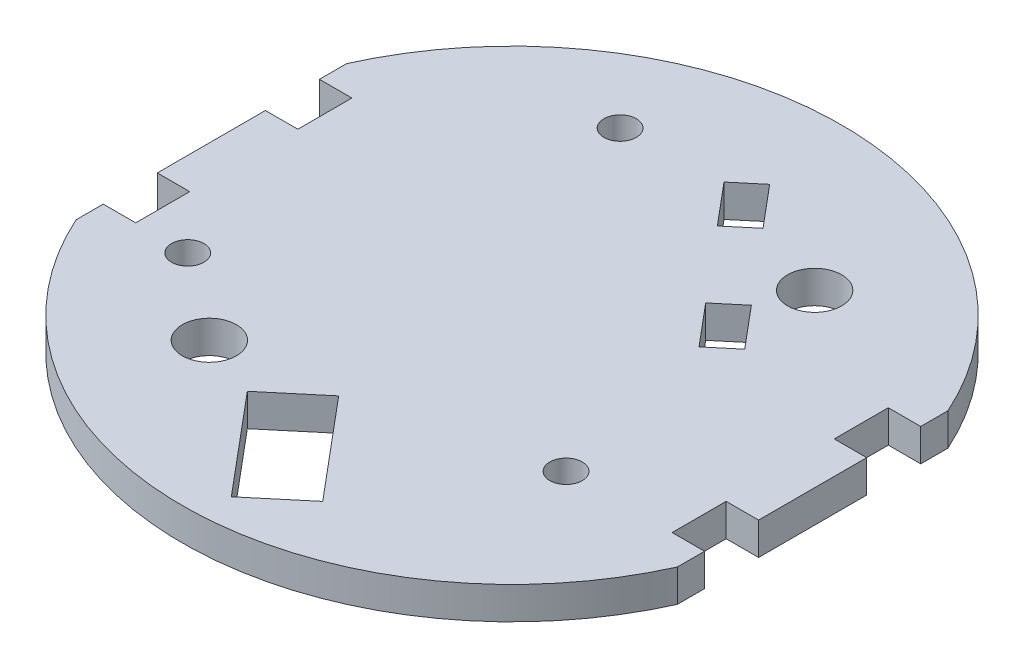
SolidWorks part; units mm, degrees
ref_plane "Alzado" through (0, 0, 0) normal (0, 0, 1) x (1, 0, 0)
ref_plane "Planta" through (0, 0, 0) normal (0, 1, 0) x (1, 0, 0)
ref_plane "Vista lateral" through (0, 0, 0) normal (1, 0, 0) x (0, 0, -1)
sketch "Croquis1" plane through (0, 0, 0) normal (0, 1, 0) x (1, 0, 0)
  circle A0 centre (0, 0) radius 30.5
extrude "Saliente-Extruir1" add sketch "Croquis1" along normal blind 3
sketch "Croquis5" plane through (0, 3, 0) normal (0, 1, 0) x (1, 0, 0)
  line L0 (0, 0) -> (0, 10)
  line L1 (28.8141, -5) -> (30.0874, -5)
  line L2 (28.8141, 5) -> (30.0874, 5)
  line L3 (-24.8141, 10) -> (-28.8141, 10)
  line L4 (24.8141, -5) -> (24.8141, -10)
  line L5 (-24.8141, -10) -> (-28.8141, -10)
  line L6 (24.8141, -5) -> (28.8141, -5)
  line L7 (24.8141, 5) -> (24.8141, 10)
  line L8 (-24.8141, 5) -> (-28.8141, 5)
  line L9 (-24.8141, 5) -> (-24.8141, 10)
  line L10 (-24.8141, -5) -> (-28.8141, -5)
  line L11 (-24.8141, -5) -> (-24.8141, -10)
  line L12 (24.8141, 5) -> (28.8141, 5)
  line L13 (24.8141, -10) -> (28.8141, -10)
  line L14 (24.8141, 10) -> (28.8141, 10)
  line L15 (-28.8141, 5) -> (-30.0874, 5)
  line L16 (-28.8141, -5) -> (-30.0874, -5)
  circle A1 centre (0, 0) radius 30.5 construction
  arc A2 (-28.8141, 10) -> (-30.0874, 5) centre (0, 0) ccw
  arc A3 (28.8141, 10) -> (28.8141, -10) centre (0, 0) cw
  arc A4 (-30.0874, -5) -> (-28.8141, -10) centre (0, 0) ccw
  arc A5 (30.0874, -5) -> (28.8141, -10) centre (0, 0) cw
  arc A6 (28.8141, 10) -> (30.0874, 5) centre (0, 0) cw
  circle M2 centre (0, 0) radius 30.5
extrude "Cortar-Extruir3" cut sketch "Croquis5" against normal blind 4 contours L11 L10 L8 L9 L3 L5 M2 | L15 L8 L9 L3 M2 | L14 L7 L12 L2 M2 | L4 L13 L1 L6 M2 region at (27.1844, 3, 7.3876) region at (27.1844, 3, -7.3876) region at (-27.1844, 3, 7.3876) region at (-27.1844, 3, -7.3876)
sketch "Croquis7" plane through (0, 3, 0) normal (0, 1, 0) x (1, 0, 0)
  line L0 (-8.1011, 29.1011) -> (9.5756, 8.0348)
  line L1 (9.5756, 8.0348) -> (27.2522, -13.0314)
  line L2 (-8.1011, 29.1011) -> (-27.2522, 13.0314)
  line L3 (27.2522, -13.0314) -> (8.1011, -29.1011)
  line L4 (8.1011, -29.1011) -> (-27.2522, 13.0314)
  line L5 (1.4284, 22.4114) -> (-0.8697, 20.4831)
  line L6 (1.4284, 22.4114) -> (4.6423, 18.5812)
  line L7 (4.6423, 18.5812) -> (2.3442, 16.6528)
  line L8 (2.3442, 16.6528) -> (-0.8697, 20.4831)
  line L9 (7.9686, 9.95) -> (11.1825, 6.1197)
  line L10 (8.1011, -29.1011) -> (5.53, -26.0369)
  line L11 (10.2667, 11.8783) -> (13.4807, 8.0481)
  line L12 (13.4807, 8.0481) -> (11.1825, 6.1197)
  line L13 (10.2667, 11.8783) -> (7.9686, 9.95)
  line L14 (5.53, -26.0369) -> (10.8923, -21.5374)
  line L15 (10.8923, -21.5374) -> (-19.3188, 14.4667)
  line L17 (-24.6811, 9.9672) -> (-19.3188, 14.4667)
  point P7 (-9.5756, -8.0348)
extrude "Cortar-Extruir5" cut sketch "Croquis7" against normal blind 4 contours L7 L6 L5 L0 | L11 L13 L0 L1 L12 region at (1.8863, 3, -19.5321) region at (10.7246, 3, -8.999)
sketch "Croquis8" plane through (0, 3, 0) normal (0, 1, 0) x (1, 0, 0)
  line L0 (-11.3137, 11.3137) -> (0, 0)
  line L2 (0, 0) -> (12, 0)
  line L3 (0, 0) -> (-11.3137, 11.3137)
  line L4 (12, 0) -> (12, 16)
  line L5 (0, 0) -> (-12, 0)
  line L6 (-12, 0) -> (-12, -16)
  line L10 (1.5586, -27.5246) -> (6.1549, -23.6679)
  line L11 (6.1549, -23.6679) -> (-1.5586, -14.4754)
  line L13 (-6.1549, -18.3321) -> (-1.5586, -14.4754)
  line L14 (1.5586, -27.5246) -> (-6.1549, -18.3321)
  circle A0 centre (0, 0) radius 30
  circle A1 centre (0, 0) radius 16
  circle A2 centre (0, 0) radius 24
  circle A3 centre (-12, -16) radius 2.5
  circle A4 centre (0, 0) radius 20
  circle A5 centre (12, 16) radius 2.5
  point P20 (-3.8567, -16.4037)
extrude "Cortar-Extruir6" cut sketch "Croquis8" against normal blind 10 contours L13 A4 L10 L11 | A4 A3 | L6 A4 A3 | A3 A4 L6 | A4 A5 | L4 A5 A4 | A4 A5 L4 | A2 L14 L10 L11 | A4 L14 A2 L11 | L13 A1 L11 region at (10.8019, 3, -15.3654) region at (12.6835, 3, -14.5491) region at (-10.8019, 3, 15.3654) region at (-12.6835, 3, 14.5491) region at (-1.7552, 3, 18.1481) region at (-1.6254, 3, 15.4208) region at (12.6194, 3, -16.8259) region at (-12.6194, 3, 16.8259) region at (0.4942, 3, 21.8146) region at (2.2344, 3, 25.0251)
sketch "Croquis9" plane through (0, 3, 0) normal (0, 1, 0) x (1, 0, 0)
  line L0 (0, 0) -> (0, 20)
  line L1 (0, 20) -> (-10, 20)
  line L2 (0, 0) -> (-20, 0)
  line L3 (-20, 0) -> (-20, -10)
  line L4 (0, 0) -> (15, 0)
  line L5 (15, 0) -> (15, -10)
  circle A0 centre (-10, 20) radius 1.5
  circle A1 centre (-20, -10) radius 1.5
  circle A2 centre (15, -10) radius 1.5
extrude "Cortar-Extruir7" cut sketch "Croquis9" against normal blind 3 contours A1 | A2 | A0 region at (-18.9693, 3, 8.9693) region at (16.0307, 3, 8.9693)
sketch "Croquis10" plane through (0, 3, 0) normal (0, 1, 0) x (1, 0, 0)
  line L0 (-24.8141, 10) -> (-27.8141, 10)
  line L2 (-24.8141, 10) -> (-28.8141, 10) construction
  line L4 (-27.8141, 10) -> (-27.8141, 12.5151)
  line L6 (-27.8141, 10) -> (-28.8141, 10)
  line L9 (-24.8141, 5) -> (-30.0874, 5) construction
  line L10 (-27.8141, 5) -> (-27.8141, -5)
  line L11 (-24.8141, -5) -> (-30.0874, -5) construction
  line L12 (-27.8141, -5) -> (-30.0874, -5)
  line L13 (-27.8141, 5) -> (-30.0874, 5)
  line L14 (-27.8141, -10) -> (-28.8141, -10)
  line L15 (-27.8141, -10) -> (-27.8141, -12.5151)
  line L16 (27.8141, -10) -> (27.8141, -12.5151)
  line L17 (27.8141, -10) -> (28.8141, -10)
  line L18 (27.8141, 5) -> (30.0874, 5)
  line L19 (27.8141, -5) -> (30.0874, -5)
  line L20 (27.8141, 5) -> (27.8141, -5)
  line L21 (27.8141, 10) -> (28.8141, 10)
  line L22 (27.8141, 10) -> (27.8141, 12.5151)
  line L23 (24.8141, 10) -> (27.8141, 10)
  arc A2 (28.8141, 10) -> (-28.8141, 10) centre (0, 0) ccw construction
  arc A5 (-27.8141, 12.5151) -> (-28.8141, 10) centre (0, 0) ccw
  arc A6 (-30.0874, 5) -> (-30.0874, -5) centre (0, 0) ccw
  arc A7 (-27.8141, -12.5151) -> (-28.8141, -10) centre (0, 0) cw
  arc A8 (27.8141, -12.5151) -> (28.8141, -10) centre (0, 0) ccw
  arc A9 (30.0874, 5) -> (30.0874, -5) centre (0, 0) cw
  arc A10 (27.8141, 12.5151) -> (28.8141, 10) centre (0, 0) cw
  line M9 (24.8141, -5) -> (30.0874, -5)
  arc M10 (30.0874, -5) -> (30.0874, 5) centre (0, 0) ccw
  line M11 (30.0874, 5) -> (24.8141, 5)
  line M13 (24.8141, 10) -> (28.8141, 10)
  arc M14 (28.8141, 10) -> (-28.8141, 10) centre (0, 0) ccw
  line M15 (-28.8141, 10) -> (-24.8141, 10)
  line M17 (-24.8141, 5) -> (-30.0874, 5)
  arc M18 (-30.0874, 5) -> (-30.0874, -5) centre (0, 0) ccw
  line M19 (-30.0874, -5) -> (-24.8141, -5)
  line M21 (-24.8141, -10) -> (-28.8141, -10)
  arc M22 (-28.8141, -10) -> (28.8141, -10) centre (0, 0) ccw
  line M23 (28.8141, -10) -> (24.8141, -10)
extrude "Cortar-Extruir8" cut sketch "Croquis10" against normal blind 3 contours L15 M21 M22 | L10 M17 M18 M19 | L4 M15 M14 | L16 M23 M22 | L20 M11 M9 M10 | L22 M13 M14 | L22 A10 L21 region at (-28.1547, 3, -10.8559) region at (28.1547, 3, -10.8559) region at (-29.0914, 3, 0) region at (-28.1547, 3, 10.8559) region at (28.1547, 3, 10.8559) region at (29.0914, 3, 0)
